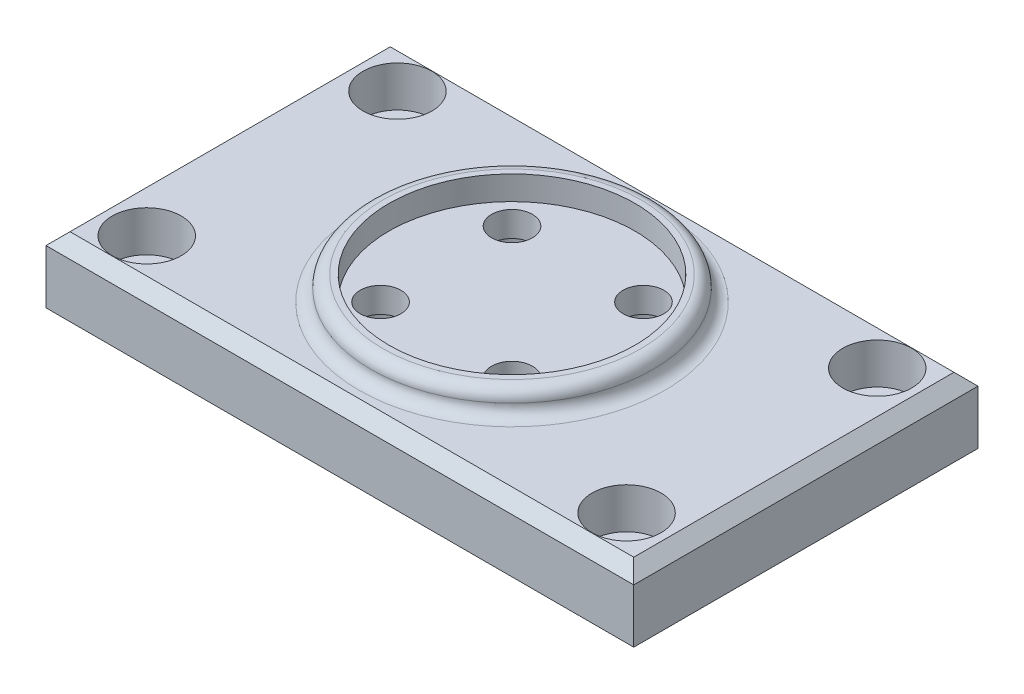
SolidWorks part; units mm, degrees
ref_plane "Front Plane" through (0, 0, 0) normal (0, 0, 1) x (1, 0, 0)
ref_plane "Top Plane" through (0, 0, 0) normal (0, 1, 0) x (1, 0, 0)
ref_plane "Right Plane" through (0, 0, 0) normal (1, 0, 0) x (0, 0, -1)
sketch "Sketch1" plane through (0, 0, 0) normal (0, 1, 0) x (1, 0, 0)
  line L1 (24.5, -14.35) -> (-24.5, -14.35)
  line L2 (24.5, -14.35) -> (24.5, 14.35)
  line L3 (24.5, 14.35) -> (-24.5, 14.35)
  line L4 (-24.5, -14.35) -> (-24.5, 14.35)
  line L5 (24.5, -14.35) -> (-24.5, 14.35) construction
  line L6 (24.5, 14.35) -> (-24.5, -14.35) construction
  point P0 (0, 0)
  dimension "D1" = 28.7
  dimension "D2" = 49
extrude "Boss-Extrude1" add sketch "Sketch1" along normal blind 5.5
hole_wizard "CBORE for M3 SHCS1" positions "Sketch3" profile "Sketch4" counterbore size "M3" standard "ANSI Metric"
sketch "Sketch3" plane through (0, 5.5, 0) normal (0, 1, 0) x (1, 0, 0)
  line L1 (20, -10.45) -> (-20, -10.45)
  line L2 (20, -10.45) -> (20, 10.45)
  line L3 (20, 10.45) -> (-20, 10.45)
  line L4 (-20, -10.45) -> (-20, 10.45)
  line L5 (20, -10.45) -> (-20, 10.45) construction
  line L6 (20, 10.45) -> (-20, -10.45) construction
  point P0 (-20, 10.45)
  point P2 (20, 10.45)
  point P4 (20, -10.45)
  point P6 (-20, -10.45)
  point P9 (0, 0)
  dimension "D1" = 20.9
  dimension "D2" = 40
sketch "Sketch4" plane through (-20, 5.5, -10.45) normal (1, 0, 0) x (0, 0, 1)
  line L0 (0, 0) -> (0, 5.5)
  line L1 (0, 5.5) -> (1.7, 5.5)
  line L3 (1.7, 5.5) -> (1.7, 3.4)
  line L4 (1.7, 3.4) -> (2.875, 3.4)
  line L5 (2.875, 3.4) -> (2.875, 0)
  line L7 (2.875, 0) -> (0, 0)
  line L11 (0, -6.35) -> (0, 107.95) construction
  dimension "Thru Hole Dia." = 3.4
  dimension "Thru Hole Depth" = 5.5
  dimension "C'Bore Dia." = 5.75
  dimension "C'Bore Depth" = 3.4
sketch "Sketch5" plane through (0, 0, 0) normal (0, 1, 0) x (1, 0, 0)
  circle A0 centre (0, 0) radius 10
  dimension "D1" = 20
sketch "Sketch7" plane through (0, 0, 0) normal (0, -1, 0) x (-1, 0, 0)
  line L1 (5.4801, 5.4801) -> (-5.4801, 5.4801)
  line L2 (5.4801, 5.4801) -> (5.4801, -5.4801)
  line L3 (5.4801, -5.4801) -> (-5.4801, -5.4801)
  line L4 (-5.4801, 5.4801) -> (-5.4801, -5.4801)
  line L5 (5.4801, 5.4801) -> (-5.4801, -5.4801) construction
  line L6 (5.4801, -5.4801) -> (-5.4801, 5.4801) construction
  circle A2 centre (0, 0) radius 7.75
  point P0 (-5.4801, -5.4801)
  point P2 (5.4801, -5.4801)
  point P4 (5.4801, 5.4801)
  point P6 (-5.4801, 5.4801)
  point P90 (0, 0)
  point P91 (-5.1757, 5.0768)
  point P92 (-5.1757, -5.0768)
  point P93 (5.1757, -5.0768)
  point P94 (5.1757, 5.0768)
  dimension "D3" = 15.5
hole_wizard "CBORE for M3 SHCS2" positions "Sketch7" profile "Sketch8" counterbore size "M3" standard "ANSI Metric" end condition through all
sketch "Sketch8" plane through (5.4801, 0, 5.4801) normal (1, 0, 0) x (0, 0, -1)
  line L0 (0, 0) -> (0, 5.5)
  line L1 (0, 5.5) -> (1.7, 5.5)
  line L3 (1.7, 5.5) -> (1.7, 3.4)
  line L4 (1.7, 3.4) -> (2.875, 3.4)
  line L5 (2.875, 3.4) -> (2.875, 0)
  line L7 (2.875, 0) -> (0, 0)
  line L11 (0, -6.35) -> (0, 107.95) construction
  dimension "Thru Hole Dia." = 3.4
  dimension "Thru Hole Depth" = 5.5
  dimension "C'Bore Dia." = 5.75
  dimension "C'Bore Depth" = 3.4
sketch "Sketch9" plane through (0, 5.5, 0) normal (0, 1, 0) x (1, 0, 0)
  circle A0 centre (0, 0) radius 11.75
  circle A1 centre (0, 0) radius 10.25
  dimension "D1" = 20.5
  dimension "D2" = 23.5
extrude "Boss-Extrude2" add sketch "Sketch9" along normal blind 2
fillet "Fillet1" radius 1 2 edges at (0, 7.5, 11.75) (0, 5.5, 11.75)
chamfer "Chamfer1" distance 1 angle 45 4 edges at (24.5, 5.5, 0) (0, 5.5, -14.35) (-24.5, 5.5, 0) (0, 5.5, 14.35)
